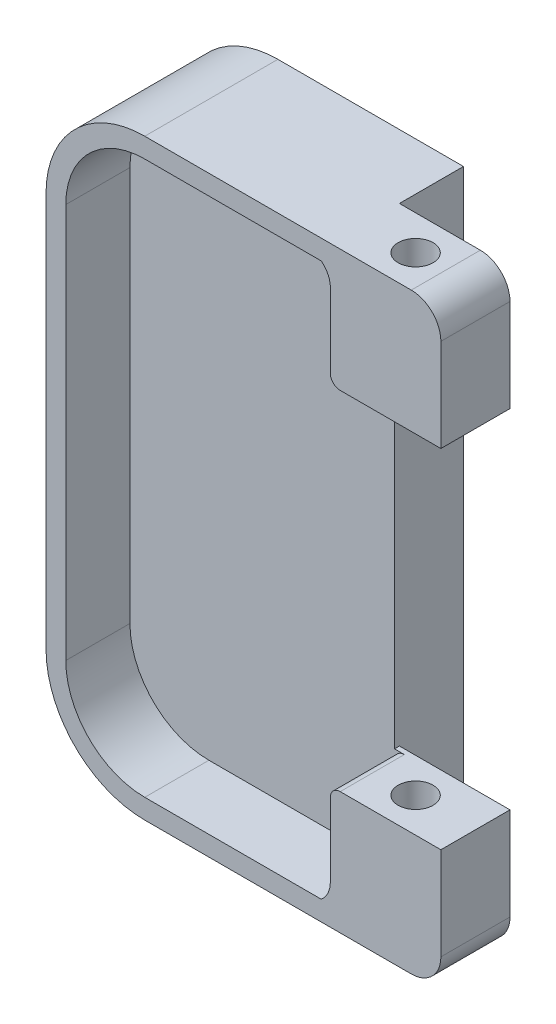
SolidWorks part; units mm, degrees
ref_plane "Front Plane" through (0, 0, 0) normal (0, 0, 1) x (1, 0, 0)
ref_plane "Top Plane" through (0, 0, 0) normal (0, 1, 0) x (1, 0, 0)
ref_plane "Right Plane" through (0, 0, 0) normal (1, 0, 0) x (0, 0, -1)
sketch "Sketch1" plane through (0, 0, 0) normal (0, 0, 1) x (1, 0, 0)
  line L1 (57.15, -22.225) -> (-57.15, -22.225)
  line L2 (57.15, -22.225) -> (57.15, 22.225)
  line L3 (57.15, 22.225) -> (-57.15, 22.225)
  line L4 (-57.15, -22.225) -> (-57.15, 22.225)
  line L5 (57.15, -22.225) -> (-57.15, 22.225) construction
  line L6 (57.15, 22.225) -> (-57.15, -22.225) construction
  point P0 (0, 0)
  dimension "D1" = 44.45
  dimension "D2" = 114.3
extrude "Boss-Extrude1" add sketch "Sketch1" along normal blind 62.23
sketch "Sketch2" plane through (0, 0, 62.23) normal (0, 0, 1) x (1, 0, 0)
  line L0 (-57.15, 22.225) -> (-57.15, -22.225) construction
  line L1 (57.15, -15.025) -> (-57.15, -15.025)
  line L2 (57.15, -15.025) -> (57.15, 15.025)
  line L3 (57.15, 15.025) -> (-57.15, 15.025)
  line L4 (-57.15, -15.025) -> (-57.15, 15.025)
  line L5 (57.15, -15.025) -> (-57.15, 15.025) construction
  line L6 (57.15, 15.025) -> (-57.15, -15.025) construction
  line L7 (57.15, 22.225) -> (-57.15, 22.225) construction
  point P0 (0, 0)
  dimension "D1" = 7.2
extrude "Cut-Extrude2" cut sketch "Sketch2" against normal blind 31.75
sketch "Sketch3" plane through (0, 0, 0) normal (0, 0, -1) x (-1, 0, 0)
  line L0 (-57.15, -22.225) -> (-57.15, 22.225) construction
  line L1 (57.15, 22.225) -> (-57.15, 22.225)
  line L2 (57.15, 22.225) -> (57.15, -9.525)
  line L3 (57.15, -9.525) -> (-57.15, -9.525)
  line L4 (-57.15, 22.225) -> (-57.15, -9.525)
  line L5 (57.15, -22.225) -> (-57.15, -22.225) construction
  dimension "D1" = 12.7
extrude "Cut-Extrude3" cut sketch "Sketch3" against normal blind 21.59
sketch "Sketch7" plane through (0, -22.225, 0) normal (0, -1, 0) x (1, 0, 0)
  line L0 (57.15, 62.23) -> (57.15, 0) construction
  line L1 (-57.15, 0) -> (57.15, 0) construction
  circle A0 centre (31.75, 50.36) radius 4.8
  circle A1 centre (-27.14, 39.37) radius 4.8
  dimension "D1" = 9.6
  dimension "D2" = 25.4
  dimension "D3" = 39.37
  dimension "D4" = 9.6
  dimension "D5" = 58.89
  dimension "D6" = 10.99
extrude "Cut-Extrude6" cut sketch "Sketch7" against normal up to surface (44.45 mm away) up to face at (0, 22.225, 41.91)
sketch "Sketch9" plane through (0, 0, 30.48) normal (0, 0, 1) x (1, 0, 0)
  line L5 (57.15, 15.025) -> (-57.15, 15.025) construction
  line L6 (-38.1, 15.025) -> (6.35, 15.025)
  line L7 (-38.1, 15.025) -> (-38.1, -15.025)
  line L8 (-38.1, -15.025) -> (6.35, -15.025)
  line L9 (6.35, 15.025) -> (6.35, -15.025)
  line L10 (-57.15, -15.025) -> (57.15, -15.025) construction
  line L11 (-57.15, 15.025) -> (-57.15, -15.025) construction
  line L12 (57.15, -15.025) -> (57.15, 15.025) construction
  dimension "D1" = 50.8
  dimension "25in" = 19.05
extrude "Cut-Extrude7" cut sketch "Sketch9" against normal through all both and the other way through all
sketch "Sketch16" plane through (0, -22.225, 0) normal (0, -1, 0) x (1, 0, 0)
  line L1 (-38.1, 30.48) -> (-57.15, 30.48) construction
  line L8 (-57.15, 62.23) -> (57.15, 62.23)
  line L9 (57.15, 62.23) -> (57.15, 47.0103)
  line L10 (57.15, 62.23) -> (57.15, 0) construction
  line L11 (-15.99, 39.37) -> (21.87, 50.36)
  line L12 (41.63, 50.36) -> (57.15, 47.0103)
  line L13 (-48.4121, 30.48) -> (-57.15, 30.48)
  line L15 (-57.15, 30.48) -> (-57.15, 62.23)
  arc A2 (41.63, 50.36) -> (21.87, 50.36) centre (31.75, 50.36) ccw
  arc A3 (-15.99, 39.37) -> (-38.2702, 40.0345) centre (-27.14, 39.37) ccw
  circle A4 centre (-27.14, 39.37) radius 4.8 construction
  circle A5 centre (31.75, 50.36) radius 4.8 construction
  arc A6 (-48.4121, 30.48) -> (-38.2702, 40.0345) centre (-48.4121, 40.64) ccw
  dimension "D1" = 6.35
  dimension "D2" = 5.08
  dimension "D3" = 10.16
extrude "Cut-Extrude8" cut sketch "Sketch16" against normal through all
sketch "Sketch14" plane through (6.35, 0, 0) normal (-1, 0, 0) x (0, 0, 1)
  line L0 (0, -15.025) -> (30.48, -15.025) construction
  line L1 (21.59, -9.525) -> (0, -9.525)
  line L2 (21.59, -9.525) -> (21.59, -15.025)
  line L3 (21.59, -15.025) -> (0, -15.025)
  line L4 (0, -9.525) -> (0, -15.025)
extrude "Boss-Extrude2" add sketch "Sketch14" along normal up to next
sketch "Sketch17" plane through (0, 0, 21.59) normal (0, 0, 1) x (1, 0, 0)
  line L1 (6.35, -15.025) -> (-38.1, -15.025)
  line L2 (6.35, -15.025) -> (6.35, -9.525)
  line L3 (6.35, -9.525) -> (-38.1, -9.525)
  line L4 (-38.1, -15.025) -> (-38.1, -9.525)
extrude "Boss-Extrude3" add sketch "Sketch17" along normal up to surface (8.89 mm away) up to face at (31.75, 0, 30.48)
sketch "Sketch18" plane through (-57.15, 0, 0) normal (-1, 0, 0) x (0, 0, 1)
  line L0 (30.48, 22.225) -> (30.48, -22.225) construction
  line L1 (21.59, 22.225) -> (30.48, 22.225)
  line L2 (21.59, 22.225) -> (21.59, -22.225)
  line L3 (21.59, -22.225) -> (30.48, -22.225)
  line L4 (30.48, 22.225) -> (30.48, -22.225)
  line L5 (21.59, 22.225) -> (30.48, -22.225) construction
  line L6 (21.59, -22.225) -> (30.48, 22.225) construction
  line L7 (30.48, -22.225) -> (0, -22.225) construction
  line L8 (21.59, -9.525) -> (21.59, 22.225) construction
  line L9 (30.48, 22.225) -> (21.59, 22.225) construction
  point P0 (26.035, 0)
sketch "Sketch20" plane through (0, 0, 21.59) normal (0, 0, -1) x (-1, 0, 0)
  line L0 (38.1, 15.025) -> (38.1, -9.525) construction
  line L1 (38.1, 38.1) -> (88.9, 38.1)
  line L2 (38.1, 38.1) -> (38.1, -38.1)
  line L3 (38.1, -38.1) -> (88.9, -38.1)
  line L4 (88.9, 38.1) -> (88.9, -38.1)
  line L5 (38.1, 38.1) -> (88.9, -38.1) construction
  line L6 (38.1, -38.1) -> (88.9, 38.1) construction
  point P0 (63.5, 0)
  point P9 (88.9, 0)
  dimension "D1" = 76.2
  dimension "D2" = 50.8
extrude "Boss-Extrude5" add sketch "Sketch20" against normal up to vertex (8.89 mm away) up to point (-57.15, 22.225, 30.48)
fillet "Fillet4" radius 12.7 2 edges at (-88.9, -38.1, 26.035) (-88.9, 38.1, 26.035)
sketch "Sketch21" plane through (0, 0, 30.48) normal (0, 0, 1) x (1, 0, 0)
  line L0 (-40.64, -35.56) -> (-40.64, -24.765)
  line L9 (-76.2, -35.56) -> (-40.64, -35.56)
  line L16 (-50.9521, -12.485) -> (-40.64, -12.485)
  line L17 (-40.64, -12.485) -> (-40.64, -12.065)
  line L21 (-76.2, -35.56) -> (-40.64, -35.56)
  line L22 (-40.64, -35.56) -> (-40.64, -24.765)
  line L23 (-40.64, -24.765) -> (-50.9521, -24.765)
  line L24 (-40.64, -24.765) -> (-50.9521, -24.765)
  line L25 (-50.9521, -24.765) -> (-50.9521, -12.485)
  line L26 (-50.9521, -24.765) -> (-50.9521, -12.485)
  line L27 (-50.9521, 12.485) -> (-50.9521, 24.765)
  line L28 (-50.9521, 12.485) -> (-50.9521, 24.765)
  line L29 (-50.9521, 24.765) -> (-40.64, 24.765)
  line L30 (-50.9521, 24.765) -> (-40.64, 24.765)
  line L31 (-40.64, 24.765) -> (-40.64, 35.56)
  line L32 (-40.64, 24.765) -> (-40.64, 35.56)
  line L33 (-40.64, 35.56) -> (-76.2, 35.56)
  line L36 (-50.9521, -12.485) -> (54.61, -12.485)
  line L37 (54.61, -12.485) -> (54.61, 12.485)
  line L38 (54.61, 12.485) -> (8.89, 12.485)
  line L39 (8.89, 12.485) -> (8.89, -12.065)
  line L40 (8.89, -12.065) -> (-40.64, -12.065)
  line L41 (-40.64, -12.065) -> (-40.64, 12.485)
  line L42 (-40.64, 12.485) -> (-50.9521, 12.485)
  line L43 (-40.64, 35.56) -> (-76.2, 35.56)
  line L44 (-86.36, 25.4) -> (-86.36, -25.4)
  line L45 (-86.36, 25.4) -> (-86.36, -25.4)
  line L57 (-40.64, -12.065) -> (-40.64, 12.485)
  line L58 (-40.64, 12.485) -> (-50.9521, 12.485)
  arc A9 (-76.2, 35.56) -> (-86.36, 25.4) centre (-76.2, 25.4) ccw
  arc A10 (-76.2, 35.56) -> (-86.36, 25.4) centre (-76.2, 25.4) ccw
  arc A11 (-86.36, -25.4) -> (-76.2, -35.56) centre (-76.2, -25.4) ccw
  arc A16 (-86.36, -25.4) -> (-76.2, -35.56) centre (-76.2, -25.4) ccw
  dimension "D1" = 2.54
extrude "Cut-Extrude10" cut sketch "Sketch21" against normal blind 2.54 contours L32 L43 A10 L45 A16 L21 L0 L24 L26 L16 L17 L57 L58 L28 L30 region at (-64.709, 0, 30.48)
sketch "Sketch22" plane through (0, -22.225, 0) normal (0, -1, 0) x (1, 0, 0)
  line L0 (-57.15, 0) -> (57.15, 0)
  line L1 (57.15, 0) -> (57.15, 47.0103)
  line L2 (57.15, 47.0103) -> (41.63, 50.36)
  line L3 (-15.99, 39.37) -> (21.87, 50.36)
  line L4 (-57.15, 0) -> (-57.15, 21.59)
  line L5 (-57.15, 21.59) -> (-38.1, 21.59)
  line L6 (-38.1, 21.59) -> (-38.1, 30.48)
  line L7 (-38.1, 30.48) -> (-38.2702, 40.0345)
  arc A0 (-15.99, 39.37) -> (-38.2395, 38.3096) centre (-27.14, 39.37) ccw
  arc A1 (41.63, 50.36) -> (21.87, 50.36) centre (31.75, 50.36) ccw
  point P12 (-57.15, 21.59)
  point P16 (-27.14, 39.37)
  point P23 (31.75, 50.36)
  circle M1 centre (-27.14, 39.37) radius 4.8
  circle M2 centre (31.75, 50.36) radius 4.8
  line M4 (-38.1, 30.48) -> (-38.1, 21.59)
  line M5 (-38.1, 21.59) -> (-57.15, 21.59)
  line M6 (-57.15, 21.59) -> (-57.15, 0)
  line M7 (-57.15, 0) -> (57.15, 0)
  line M8 (57.15, 0) -> (57.15, 47.0103)
  line M9 (57.15, 47.0103) -> (41.63, 50.36)
  arc M10 (41.63, 50.36) -> (21.87, 50.36) centre (31.75, 50.36) ccw
  line M11 (21.87, 50.36) -> (-15.99, 39.37)
  arc M12 (-15.99, 39.37) -> (-38.2702, 40.0345) centre (-27.14, 39.37) ccw
extrude "Cut-Extrude11" cut sketch "Sketch22" against normal through all both and the other way through all contours L7 M4 M5 M6 M7 M8 M9 M10 M11 M12 M2 M1 region at (6.3278, -22.225, 23.0639)
sketch "Sketch25" plane through (0, 0, 30.48) normal (0, 0, 1) x (1, 0, 0)
  line L1 (-48.4121, 22.225) -> (-38.1, 22.225)
  line L2 (-48.4121, 22.225) -> (-48.4121, 15.025)
  line L3 (-48.4121, 15.025) -> (-38.1, 15.025)
  line L4 (-38.1, 22.225) -> (-38.1, 15.025)
  line L5 (-48.4121, -15.025) -> (-38.1, -15.025)
  line L6 (-48.4121, -15.025) -> (-48.4121, -22.225)
  line L7 (-48.4121, -22.225) -> (-38.1, -22.225)
  line L8 (-38.1, -15.025) -> (-38.1, -22.225)
extrude "Cut-Extrude14" cut sketch "Sketch25" along normal blind 17.272 contours L6 L7 L8 L5
sketch "Sketch26" plane through (0, 0, 30.48) normal (0, 0, 1) x (1, 0, 0)
  line L1 (-48.4121, 22.225) -> (-38.1, 22.225)
  line L2 (-48.4121, 22.225) -> (-48.4121, 15.025)
  line L3 (-48.4121, 15.025) -> (-38.1, 15.025)
  line L4 (-38.1, 22.225) -> (-38.1, 15.025)
extrude "Cut-Extrude15" cut sketch "Sketch26" along normal blind 17.272
sketch "Sketch28" plane through (0, 0, 30.48) normal (0, 0, 1) x (1, 0, 0)
  line L0 (-40.64, -24.765) -> (-50.9521, -24.765)
  line L3 (-38.1, -38.1) -> (-76.2, -38.1) construction
  line L4 (-40.64, -35.56) -> (-50.9521, -35.56)
  line L5 (-76.2, -35.56) -> (-40.64, -35.56) construction
  line L6 (-40.64, -38.1) -> (-50.9521, -38.1)
  point P3 (-40.64, -38.1)
  point P18 (-50.9521, -24.765)
  point P19 (-50.9521, -35.56)
  point P21 (-50.9521, -38.1)
sketch "Sketch32" plane through (0, -38.1, 0) normal (0, -1, 0) x (1, 0, 0)
  line L0 (-50.9521, 30.48) -> (-40.64, 30.48)
  line L1 (-38.1, 30.48) -> (-38.1, 21.59) construction
  circle A0 centre (-45.7961, 26.035) radius 2.2479
  point P0 (-40.64, 30.48)
  point P1 (-50.9521, 30.48)
  point P6 (-45.7961, 30.48)
  point P9 (-38.1, 26.035)
  dimension "D1" = 4.4958
extrude "Cut-Extrude16" cut sketch "Sketch32" against normal through all both and the other way through all contours A0
fillet "Fillet5" radius 3.81 2 edges at (-38.1, 38.1, 26.035) (-38.1, -38.1, 26.035)
sketch "Sketch33" plane through (0, 0, 30.48) normal (0, 0, 1) x (1, 0, 0)
  line L0 (-38.1, 34.29) -> (-38.1, -34.29) construction
  line L1 (-38.1, 0) -> (-38.1, 22.352)
  line L2 (-38.1, 0) -> (-38.1, -22.352)
  line L4 (-38.1, 22.352) -> (-53.467, 22.352)
  line L5 (-38.1, 22.352) -> (-38.1, -22.352)
  line L6 (-38.1, -22.352) -> (-53.467, -22.352)
  line L7 (-53.467, 22.352) -> (-53.467, -22.352)
  line L8 (-53.467, 22.352) -> (-38.1, 22.352)
  line L9 (-53.467, 22.352) -> (-53.467, -22.352)
  line L10 (-53.467, -22.352) -> (-38.1, -22.352)
  line L11 (-38.1, 22.352) -> (-38.1, -22.352)
  point P0 (-38.1, 0)
  line M4 (-38.1, -34.29) -> (-38.1, 34.29)
  line M18 (-50.9521, 12.485) -> (-40.64, 12.485)
  line M19 (-40.64, 12.485) -> (-40.64, -12.485)
  line M20 (-40.64, -12.485) -> (-50.9521, -12.485)
  dimension "D1" = 22.352
  dimension "D2" = 22.352
  dimension "D3" = 15.367
extrude "Cut-Extrude22" cut sketch "Sketch33" against normal through all contours L4 L7 L6 M18 M19 M20 M4 | L7 M18 M20 M19 region at (-45.7835, 0, 30.48)
sketch "Sketch38" plane through (0, -35.56, 0) normal (0, 1, 0) x (1, 0, 0)
  line L0 (-46.9894, -27.94) -> (-47.6244, -27.94)
  line L1 (-76.2, -27.94) -> (-46.9894, -27.94) construction
  line L2 (-44.6027, -27.94) -> (-43.9677, -27.94)
  line L3 (-44.6027, -27.94) -> (-40.64, -27.94) construction
  arc A0 (-44.6027, -27.94) -> (-46.9894, -27.94) centre (-45.7961, -26.7924) cw
  arc A1 (-43.9677, -27.94) -> (-47.6244, -27.94) centre (-45.7961, -26.1768) cw
  point P0 (-44.6027, -27.94)
  point P1 (-46.9894, -27.94)
  point P10 (-45.7961, -28.448)
  point P14 (-45.7961, -29.083)
  point P15 (-45.7961, -29.083)
  dimension "D4" = 2.54
  dimension "D1" = 0.635
  dimension "D2" = 0.635
  dimension "D3" = 0.635
sketch "Sketch39" plane through (0, 35.56, 0) normal (0, -1, 0) x (1, 0, 0)
  line L0 (-46.9894, 27.94) -> (-47.6244, 27.94)
  line L1 (-46.9894, 27.94) -> (-76.2, 27.94) construction
  line L2 (-44.6027, 27.94) -> (-43.9677, 27.94)
  line L3 (-40.64, 27.94) -> (-44.6027, 27.94) construction
  arc A0 (-46.9894, 27.94) -> (-44.6027, 27.94) centre (-45.7961, 26.7924) cw
  arc A1 (-47.6244, 27.94) -> (-43.9677, 27.94) centre (-45.7961, 26.1768) cw
  point P0 (-46.9894, 27.94)
  point P1 (-44.6027, 27.94)
  point P10 (-45.7961, 28.448)
  point P14 (-45.7961, 29.083)
  dimension "D4" = 2.54
  dimension "D1" = 0.635
  dimension "D2" = 0.635
  dimension "D3" = 0.635
sketch "Sketch41" plane through (0, -24.765, 0) normal (0, -1, 0) x (1, 0, 0)
  line L0 (-44.6027, 27.94) -> (-40.64, 27.94)
  line L1 (-50.9521, 30.48) -> (-40.64, 30.48)
  line L2 (-50.9521, 30.48) -> (-50.9521, 27.94)
  line L3 (-50.9521, 27.94) -> (-46.9894, 27.94)
  line L4 (-40.64, 30.48) -> (-40.64, 27.94)
  arc A0 (-46.9894, 27.94) -> (-44.6027, 27.94) centre (-45.7961, 25.8427) cw
  point P6 (-46.9894, 27.94)
  point P7 (-44.6027, 27.94)
extrude "Boss-Extrude6" add sketch "Sketch41" along normal blind 10.922
sketch "Sketch44" plane through (0, 24.765, 0) normal (0, 1, 0) x (1, 0, 0)
  line L0 (-44.6027, -27.94) -> (-40.64, -27.94)
  line L1 (-50.9521, -27.94) -> (-46.9894, -27.94)
  line L2 (-50.9521, -27.94) -> (-50.9521, -30.48)
  line L3 (-50.9521, -30.48) -> (-40.64, -30.48)
  line L4 (-40.64, -27.94) -> (-40.64, -30.48)
  arc A0 (-44.6027, -27.94) -> (-46.9894, -27.94) centre (-45.7961, -25.8427) cw
  point P6 (-44.6027, -27.94)
  point P7 (-46.9894, -27.94)
extrude "Boss-Extrude7" add sketch "Sketch44" along normal blind 10.922
fillet "Fillet6" radius 2.54 4 edges at (-50.9521, 22.352, 29.21) (-50.9521, -22.352, 29.21) (-50.9521, 35.56, 29.21) (-50.9521, -35.56, 29.21)
sketch "Sketch45" plane through (0, 0, 21.59) normal (0, 0, -1) x (-1, 0, 0)
  line L0 (53.467, 22.352) -> (53.467, -22.352)
  line L1 (53.467, -22.352) -> (53.467, -38.1)
  line L2 (41.91, -38.1) -> (76.2, -38.1) construction
  line L3 (53.467, -38.1) -> (76.2, -38.1)
  line L4 (53.467, 22.352) -> (53.467, 38.1)
  line L5 (76.2, 38.1) -> (41.91, 38.1) construction
  line L6 (53.467, 38.1) -> (76.2, 38.1)
  line L7 (88.9, -25.4) -> (88.9, 25.4)
  arc A0 (76.2, 38.1) -> (88.9, 25.4) centre (76.2, 25.4) cw
  arc A1 (88.9, -25.4) -> (76.2, -38.1) centre (76.2, -25.4) cw
extrude "Boss-Extrude8" add sketch "Sketch45" along normal blind 8.2423
sketch "Sketch47" plane through (0, 0, 27.94) normal (0, 0, 1) x (1, 0, 0)
  line L0 (-48.4121, 22.352) -> (-53.467, 22.352)
  line L1 (-53.467, 22.352) -> (-53.467, -22.352)
  line L2 (-53.467, -22.352) -> (-48.4121, -22.352)
  line L3 (-50.9521, 33.02) -> (-50.9521, 24.892)
  line L4 (-76.2, 35.56) -> (-53.4921, 35.56)
  line L5 (-86.36, 25.4) -> (-86.36, -25.4)
  line L6 (-76.2, -35.56) -> (-53.4921, -35.56)
  line L7 (-50.9521, -24.892) -> (-50.9521, -33.02)
  arc A0 (-48.4121, -22.352) -> (-50.9521, -24.892) centre (-48.4121, -24.892) ccw
  arc A1 (-50.9521, -33.02) -> (-53.4921, -35.56) centre (-53.4921, -33.02) cw
  arc A2 (-76.2, -35.56) -> (-86.36, -25.4) centre (-76.2, -25.4) cw
  arc A3 (-76.2, 35.56) -> (-86.36, 25.4) centre (-76.2, 25.4) ccw
  arc A4 (-53.4921, 35.56) -> (-50.9521, 33.02) centre (-53.4921, 33.02) cw
  arc A5 (-48.4121, 22.352) -> (-50.9521, 24.892) centre (-48.4121, 24.892) cw
  dimension "D1" = 10.16
  dimension "D2" = 10.16
extrude "Cut-Extrude23" cut sketch "Sketch47" against normal blind 5.715
sketch "Sketch49" plane through (-53.467, 0, 0) normal (1, 0, 0) x (0, 0, -1)
  line L0 (-21.59, 38.1) -> (-13.3477, 38.1)
  line L1 (-13.3477, 38.1) -> (-13.3477, -38.1)
  line L2 (-13.3477, -38.1) -> (-21.59, -38.1)
  line L3 (-21.59, -38.1) -> (-21.59, -22.352)
  line L4 (-21.59, 38.1) -> (-21.59, 22.352)
  line L5 (-21.59, 22.352) -> (-22.225, 22.352)
  line L6 (-22.225, 22.352) -> (-22.225, -22.352)
  line L7 (-22.225, -22.352) -> (-21.59, -22.352)
extrude "Boss-Extrude10" add sketch "Sketch49" along normal blind 1.143
sketch "Sketch50" plane through (0, 0, 22.225) normal (0, 0, 1) x (1, 0, 0)
  line L0 (-48.4121, 22.352) -> (-52.324, 22.352)
  line L1 (-52.324, 22.352) -> (-48.4121, 22.352) construction
  line L2 (-52.324, 22.352) -> (-52.324, 33.02)
  line L3 (-50.9521, 24.892) -> (-50.9521, 33.02)
  arc A0 (-50.9521, 24.892) -> (-48.4121, 22.352) centre (-48.4121, 24.892) ccw construction
  arc A1 (-52.324, 33.02) -> (-53.4921, 35.56) centre (-55.319, 33.1812) ccw
  arc A2 (-53.4921, 35.56) -> (-50.9521, 33.02) centre (-53.4921, 33.02) cw
  arc A3 (-48.4121, 22.352) -> (-50.9521, 24.892) centre (-48.4121, 24.892) cw
  dimension "D2" = 2.54
  dimension "D3" = 2.9993
  dimension "D1" = 10.668
extrude "Boss-Extrude11" add sketch "Sketch50" along normal blind 8.255
sketch "Sketch51" plane through (0, 0, 22.225) normal (0, 0, 1) x (1, 0, 0)
  line L0 (-48.4121, -22.352) -> (-52.324, -22.352)
  line L2 (-50.9521, -24.892) -> (-50.9521, -33.02)
  line L3 (-52.324, -22.352) -> (-52.324, -33.02)
  arc A1 (-48.4121, -22.352) -> (-50.9521, -24.892) centre (-48.4121, -24.892) ccw
  arc A4 (-53.4921, -35.56) -> (-50.9521, -33.02) centre (-53.4921, -33.02) ccw
  arc A5 (-53.4921, -35.56) -> (-52.324, -33.02) centre (-55.5852, -33.0588) ccw
  dimension "D1" = 3.2612
  dimension "D2" = 3.2614
extrude "Boss-Extrude12" add sketch "Sketch51" along normal blind 8.255
fillet "Fillet7" radius 1.27 2 edges at (-52.324, -22.352, 26.3525) (-52.324, 22.352, 26.3525)
